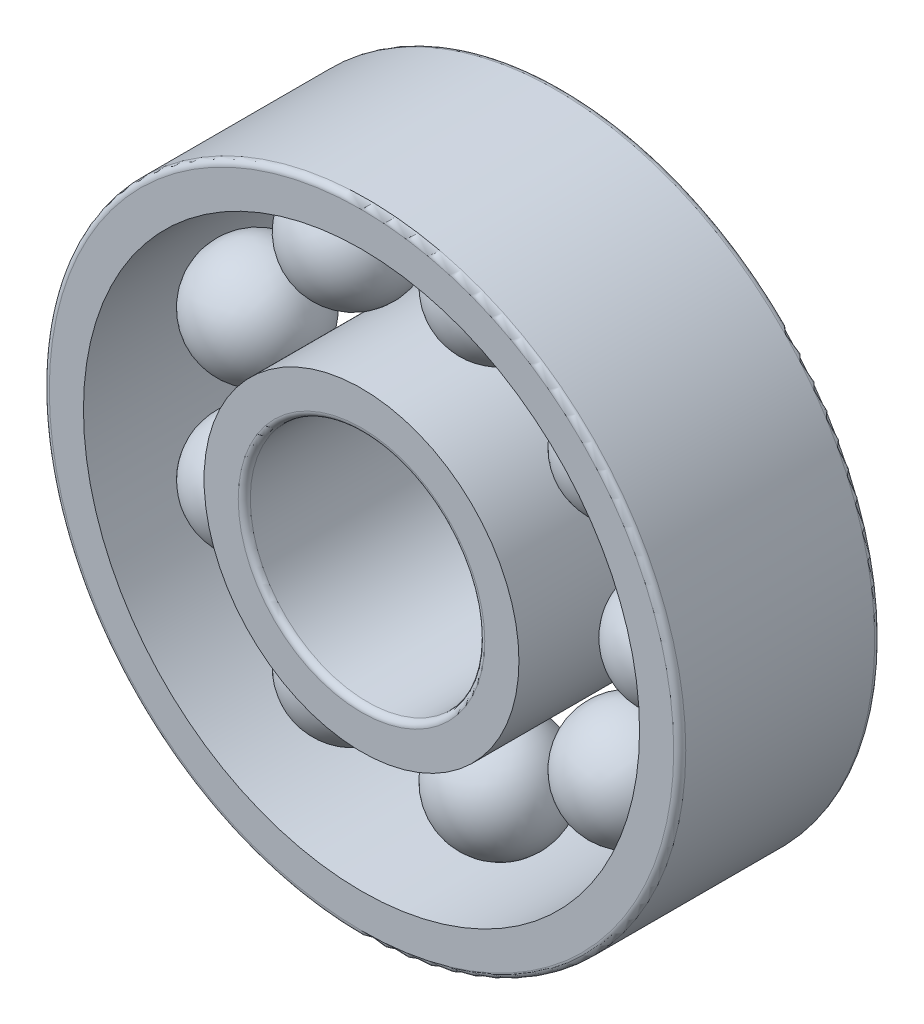
SolidWorks part; units mm, degrees
ref_plane "Front Plane" through (0, 0, 0) normal (0, 0, 1) x (1, 0, 0)
ref_plane "Top Plane" through (0, 0, 0) normal (0, 1, 0) x (1, 0, 0)
ref_plane "Right Plane" through (0, 0, 0) normal (1, 0, 0) x (0, 0, -1)
sketch "S" plane through (0, 0, 0) normal (0, 0, 1) x (1, 0, 0)
  line L0 (-3, 0) -> (3, 0) construction
  circle A0 centre (0, 0) radius 3.5 construction
  circle A1 centre (0, 0) radius 9.5 construction
  circle A2 centre (0, 0) radius 4.7 construction
  circle A3 centre (0, 0) radius 8.3 construction
  dimension "ID" = 7
  dimension "OD" = 19
  dimension "IDa" = 9.4
  dimension "ODa" = 16.6
  dimension "B" = 6
ref_axis "Z" through (0, 0, -3.3) along (0, 0, 1)
sketch "InnerS" plane through (0, 0, 0) normal (0, 1, 0) x (1, 0, 0)
  line L0 (3.5, -3) -> (4.7, -3)
  line L1 (4.7, -3) -> (4.7, 3)
  line L2 (4.7, 3) -> (3.5, 3)
  line L3 (3.5, 3) -> (3.5, -3)
  line L4 (0, -5.5) -> (0, 5.5) construction
  dimension "r1" = 3.5
  dimension "r2" = 4.7
  dimension "z1" = 3
  dimension "z2" = 3
revolve "InnerRing" add sketch "InnerS" angle 360 about L4
sketch "OuterS" plane through (0, 0, 0) normal (0, 1, 0) x (1, 0, 0)
  line L0 (8.3, -3) -> (9.5, -3)
  line L1 (9.5, -3) -> (9.5, 3)
  line L2 (9.5, 3) -> (8.3, 3)
  line L3 (8.3, 3) -> (8.3, -3)
  line L4 (0, -5.5) -> (0, 5.5) construction
  dimension "r1" = 8.3
  dimension "r2" = 9.5
  dimension "z1" = 3
  dimension "z2" = 3
revolve "OuterRing" add sketch "OuterS" angle 360 about L4
sketch "BallS" plane through (0, 0, 0) normal (0, 1, 0) x (1, 0, 0)
  line L0 (4.79, 0) -> (8.21, 0)
  arc A0 (4.79, 0) -> (8.21, 0) centre (6.5, 0) ccw
  dimension "r" = 1.71
  dimension "p" = 6.5
revolve "Ball" add sketch "BallS" angle 360 about L0
pattern_circular "BallsPattern" count 9 over 360 about axis through (0, 0, -3.3) along (0, 0, 1) of bodies 103
fillet "F1" radius 0.18 2 edges at (9.5, 0, -3) (9.5, 0, 3)
fillet "F2" radius 0.18 2 edges at (3.5, 0, -3) (3.5, 0, 3)
equation "\"r1@InnerS\" = abs(0.5*\"ID@S\")"
equation "\"r2@InnerS\" = abs(0.5*\"IDa@S\")"
equation "\"z1@InnerS\" = abs(-0.5*\"B@S\")"
equation "\"z2@InnerS\" = abs(0.5*\"B@S\")"
equation "\"r1@OuterS\" = abs(0.5*\"ODa@S\")"
equation "\"r2@OuterS\" = abs(0.5*\"OD@S\")"
equation "\"z1@OuterS\" = abs(-0.5*\"B@S\")"
equation "\"z2@OuterS\" = abs(0.5*\"B@S\")"
equation "\"r@BallS\" = abs(0.2375*\"ODa@S\"-0.2375*\"IDa@S\")"
equation "\"p@BallS\" = abs(0.25*\"IDa@S\"+0.25*\"ODa@S\")"
equation "\"N@BallsPattern\" = int(2.417*(0.25*\"IDa@S\"+0.25*\"ODa@S\")/(0.2375*\"ODa@S\"-0.2375*\"IDa@S\"))"
equation "\"r_min@F2\" = \"r_min@F1\""
